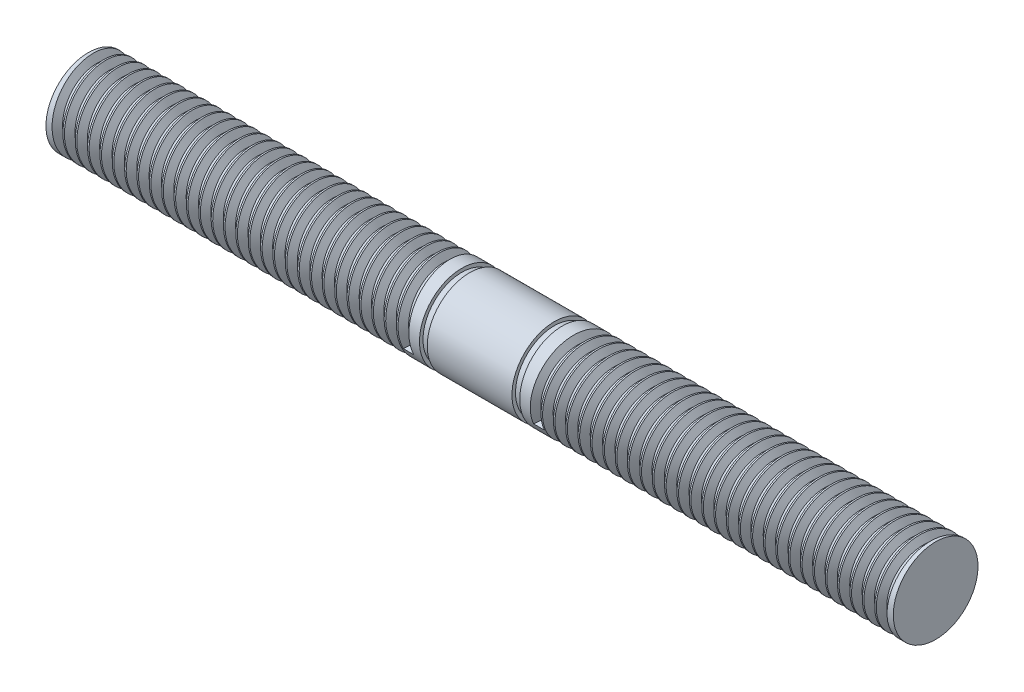
SolidWorks part; units mm, degrees
ref_plane "Front Plane" through (0, 0, 0) normal (0, 0, 1) x (1, 0, 0)
ref_plane "Top Plane" through (0, 0, 0) normal (0, 1, 0) x (1, 0, 0)
ref_plane "Right Plane" through (0, 0, 0) normal (1, 0, 0) x (0, 0, -1)
sketch "Sketch1" plane through (0, 0, 0) normal (0, 0, 1) x (1, 0, 0)
  line L0 (0, 0) -> (-60, 0) construction
  line L1 (-60, 0) -> (-60, 6)
  line L2 (-60, 6) -> (-7.1, 6)
  line L3 (0, 6) -> (0, 0)
  line L4 (-6, 6) -> (-6, 5.5)
  line L5 (-6, 5.5) -> (-7.1, 5.5)
  line L6 (-7.1, 5.5) -> (-7.1, 6)
  line L7 (-6, 6) -> (0, 6)
  line L8 (0, 0) -> (-60, 0)
  dimension "D1" = 60
  dimension "D2" = 12
  dimension "D3" = 6
  dimension "D4" = 1.1
  dimension "D5" = 11
revolve "Revolve1" add sketch "Sketch1" angle 360 about L0
thread "Thread1" pitch 1.75 method cut profile "Thread Profile1" start angle 0, offset 0, length 50, pitch 1.75, diameter 12
ref_plane "Plane1" through (-60, 0, -6) normal (0, -1, 0) x (0, 0, -1)
sketch "Thread Profile1" plane through (-60, 0, -6) normal (0, -1, 0) x (0, 0, -1)
  line L0 (0, 0) -> (0, 1.75) construction
  line L11 (0, 0) -> (0, 1.5312)
  line L12 (0, 1.5312) -> (-0.9472, 0.9844)
  line L13 (-0.9472, 0.9844) -> (-0.9472, 0.5469)
  line L15 (-0.9472, 0.5469) -> (0, 0)
  line L17 (-0.9472, 0.7656) -> (0, 0.7656) construction
  point P2 (0, 0)
  dimension "Pitch" = 1.75
  dimension "Profile_Angle" = 60
  dimension "Profile_Land" = 0.4375
  dimension "Profile_Height" = 0.9472
mirror "Mirror1" about plane through (0, 6, 0) normal (1, 0, 0) of bodies 102
